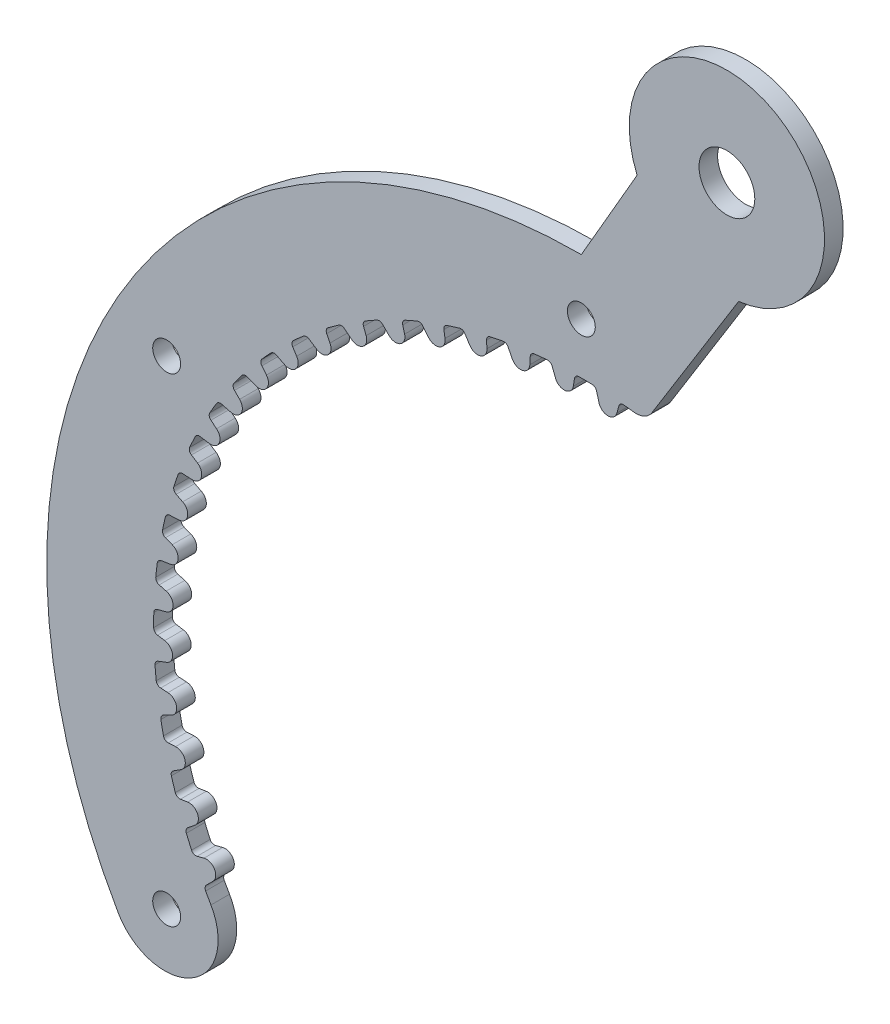
SolidWorks part; units mm, degrees
ref_plane "前视基准面" through (0, 0, 0) normal (0, 0, 1) x (1, 0, 0)
ref_plane "上视基准面" through (0, 0, 0) normal (0, 1, 0) x (1, 0, 0)
ref_plane "右视基准面" through (0, 0, 0) normal (1, 0, 0) x (0, 0, -1)
sketch "草图1" plane through (0, 0, 0) normal (0, 0, 1) x (1, 0, 0)
  line L6 (6.1601, 44.3885) -> (6.4016, 45.1318) [skipped]
  line L7 (0, 57.5) -> (6, 67.8923)
  line L10 (16.9119, 61.5923) -> (6.9151, 45.4773)
  line L11 (4.2309, 44.4896) -> (4.0233, 45.4665) [skipped]
  line L12 (3.8285, 44.65) -> (4.0308, 45.405)
  line L13 (1.8967, 44.65) -> (1.6382, 45.6147)
  line L14 (8.4748, 44.0052) -> (8.7549, 44.7349) [skipped]
  line L15 (6.5535, 44.2072) -> (6.3973, 45.1936) [skipped]
  line L16 (10.7662, 43.5014) -> (11.0841, 44.2154) [skipped]
  line L17 (8.8582, 43.8036) -> (8.7538, 44.7969) [skipped]
  line L164 (-37.109, -25.1238) -> (-37.823, -25.4417) [skipped]
  line L165 (-35.8932, -26.6252) -> (-36.4803, -27.4332) [skipped]
  line L166 (-38.373, -23.1473) -> (-39.1026, -23.4274) [skipped]
  line L167 (-37.2375, -24.7102) -> (-37.866, -25.4863) [skipped]
  line L168 (-39.5318, -21.1073) -> (-40.2752, -21.3488) [skipped]
  line L169 (-38.4797, -22.7274) -> (-39.148, -23.4697) [skipped]
  line L170 (-40.5823, -19.0094) -> (-41.3373, -19.2117)
  line L171 (-39.6164, -20.6824) -> (-40.3226, -21.3886)
  line L172 (-41.5216, -16.8594) -> (-42.2861, -17.0219) [skipped]
  line L173 (-40.6446, -18.5807) -> (-41.3868, -19.249) [skipped]
  line L174 (-42.347, -14.6633) -> (-43.119, -14.7855)
  line L175 (-41.5613, -16.4281) -> (-42.3375, -17.0566)
  line L176 (-43.0564, -12.4269) -> (-43.8337, -12.5086) [skipped]
  line L177 (-42.3641, -14.2304) -> (-43.1721, -14.8175) [skipped]
  line L178 (-43.6478, -10.1565) -> (-44.4283, -10.1974)
  line L179 (-43.0508, -11.9938) -> (-43.8884, -12.5377)
  line L180 (-44.1195, -7.8582) -> (-44.9011, -7.8582) [skipped]
  line L181 (-43.6195, -9.7242) -> (-44.4845, -10.2236) [skipped]
  line L182 (-44.4703, -5.5384) -> (-45.2508, -5.4975)
  line L183 (-44.0687, -7.428) -> (-44.9586, -7.8814)
  line L184 (-44.6992, -3.2034) -> (-45.4765, -3.1217) [skipped]
  line L185 (-44.397, -5.1115) -> (-45.3094, -5.5177) [skipped]
  line L186 (-44.8056, -0.8596) -> (-45.5776, -0.7374)
  line L187 (-44.6037, -2.7809) -> (-45.5361, -3.1388)
  line L188 (-44.7892, 1.4865) -> (-45.5537, 1.649) [skipped]
  line L189 (-44.6881, -0.4427) -> (-45.638, -0.7513) [skipped]
  line L190 (-44.65, 3.8285) -> (-45.405, 4.0308)
  line L191 (-44.65, 1.8967) -> (-45.6147, 1.6382)
  line L192 (-44.3885, 6.1601) -> (-45.1318, 6.4016) [skipped]
  line L193 (-44.4896, 4.2309) -> (-45.4665, 4.0233) [skipped]
  line L194 (-44.0052, 8.4748) -> (-44.7349, 8.7549)
  line L195 (-44.2072, 6.5535) -> (-45.1936, 6.3973)
  line L196 (-43.5014, 10.7662) -> (-44.2154, 11.0841) [skipped]
  line L197 (-43.8036, 8.8582) -> (-44.7969, 8.7538) [skipped]
  line L198 (-42.8783, 13.0282) -> (-43.5747, 13.383)
  line L199 (-43.28, 11.1385) -> (-44.2773, 11.0862)
  line L200 (-42.1377, 15.2544) -> (-42.8146, 15.6452) [skipped]
  line L201 (-42.6377, 13.3883) -> (-43.6365, 13.3883) [skipped]
  line L202 (-41.2816, 17.4388) -> (-41.9371, 17.8645)
  line L203 (-41.8786, 15.6015) -> (-42.876, 15.6538)
  line L204 (-40.3124, 19.5754) -> (-40.9447, 20.0348) [skipped]
  line L205 (-41.0047, 17.7719) -> (-41.9979, 17.8763) [skipped]
  line L206 (-39.2326, 21.6584) -> (-39.84, 22.1502)
  line L207 (-40.0184, 19.8935) -> (-41.0048, 20.0498)
  line L208 (-38.0454, 23.682) -> (-38.6262, 24.2049) [skipped]
  line L209 (-38.9224, 21.9607) -> (-39.8993, 22.1683) [skipped]
  line L210 (-36.7538, 25.6406) -> (-37.3064, 26.1933)
  line L211 (-37.7197, 23.9676) -> (-38.6844, 24.2261)
  line L212 (-35.3615, 27.529) -> (-35.8845, 28.1099) [skipped]
  line L213 (-36.4137, 25.9089) -> (-37.3635, 26.2175) [skipped]
  line L214 (-33.8723, 29.342) -> (-34.3641, 29.9494)
  line L215 (-35.0078, 27.7791) -> (-35.9402, 28.137)
  line L216 (-32.2902, 31.0745) -> (-32.7496, 31.7068) [skipped]
  line L217 (-33.506, 29.5732) -> (-34.4184, 29.9794) [skipped]
  line L218 (-30.6196, 32.7219) -> (-31.0453, 33.3773)
  line L219 (-31.9123, 31.2862) -> (-32.8022, 31.7396)
  line L220 (-28.8652, 34.2795) -> (-29.2559, 34.9564) [skipped]
  line L221 (-30.2312, 32.9135) -> (-31.0961, 33.4129) [skipped]
  line L222 (-27.0315, 35.7432) -> (-27.3864, 36.4396)
  line L223 (-28.4672, 34.4506) -> (-29.3048, 34.9945)
  line L224 (-25.1238, 37.109) -> (-25.4417, 37.823) [skipped]
  line L225 (-26.6252, 35.8932) -> (-27.4332, 36.4803) [skipped]
  line L226 (-23.1473, 38.373) -> (-23.4274, 39.1026)
  line L227 (-24.7102, 37.2375) -> (-25.4863, 37.866)
  line L228 (-21.1073, 39.5318) -> (-21.3488, 40.2752) [skipped]
  line L229 (-22.7274, 38.4797) -> (-23.4697, 39.148) [skipped]
  line L230 (-19.0094, 40.5823) -> (-19.2117, 41.3373)
  line L231 (-20.6824, 39.6164) -> (-21.3886, 40.3226)
  line L232 (-16.8594, 41.5216) -> (-17.0219, 42.2861) [skipped]
  line L233 (-18.5807, 40.6446) -> (-19.249, 41.3868) [skipped]
  line L234 (-14.6633, 42.347) -> (-14.7855, 43.119)
  line L235 (-16.4281, 41.5613) -> (-17.0566, 42.3375)
  line L236 (-12.4269, 43.0564) -> (-12.5086, 43.8337) [skipped]
  line L237 (-14.2304, 42.3641) -> (-14.8175, 43.1721) [skipped]
  line L238 (-10.1565, 43.6478) -> (-10.1974, 44.4283)
  line L239 (-11.9938, 43.0508) -> (-12.5377, 43.8884)
  line L240 (-7.8582, 44.1195) -> (-7.8582, 44.9011) [skipped]
  line L241 (-9.7242, 43.6195) -> (-10.2236, 44.4845) [skipped]
  line L242 (-5.5384, 44.4703) -> (-5.4975, 45.2508)
  line L243 (-7.428, 44.0687) -> (-7.8814, 44.9586)
  line L244 (-3.2034, 44.6992) -> (-3.1217, 45.4765) [skipped]
  line L245 (-5.1115, 44.397) -> (-5.5177, 45.3094) [skipped]
  line L246 (-0.8596, 44.8056) -> (-0.7374, 45.5776)
  line L247 (-2.7809, 44.6037) -> (-3.1388, 45.5361)
  line L248 (1.4865, 44.7892) -> (1.649, 45.5537) [skipped]
  line L249 (-0.4427, 44.6881) -> (-0.7513, 45.638) [skipped]
  line L250 (21.6584, 39.2326) -> (22.1502, 39.84) [skipped]
  line L251 (23.682, 38.0454) -> (24.2049, 38.6262) [skipped]
  line L252 (21.9607, 38.9224) -> (22.1683, 39.8993) [skipped]
  line L253 (25.6406, 36.7538) -> (26.1933, 37.3064) [skipped]
  line L254 (23.9676, 37.7197) -> (24.2261, 38.6844) [skipped]
  line L255 (27.529, 35.3615) -> (28.1099, 35.8845) [skipped]
  line L256 (25.9089, 36.4137) -> (26.2175, 37.3635) [skipped]
  line L257 (29.342, 33.8723) -> (29.9494, 34.3641) [skipped]
  line L258 (27.7791, 35.0078) -> (28.137, 35.9402) [skipped]
  line L259 (31.0745, 32.2902) -> (31.7068, 32.7496) [skipped]
  line L260 (29.5732, 33.506) -> (29.9794, 34.4184) [skipped]
  line L261 (32.7219, 30.6196) -> (33.3773, 31.0453) [skipped]
  line L262 (31.2862, 31.9123) -> (31.7396, 32.8022) [skipped]
  line L263 (34.2795, 28.8652) -> (34.9564, 29.2559) [skipped]
  line L264 (32.9135, 30.2312) -> (33.4129, 31.0961) [skipped]
  line L265 (35.7432, 27.0315) -> (36.4396, 27.3864) [skipped]
  line L266 (34.4506, 28.4672) -> (34.9945, 29.3048) [skipped]
  line L267 (37.109, 25.1238) -> (37.823, 25.4417) [skipped]
  line L268 (35.8932, 26.6252) -> (36.4803, 27.4332) [skipped]
  line L269 (38.373, 23.1473) -> (39.1026, 23.4274) [skipped]
  line L270 (37.2375, 24.7102) -> (37.866, 25.4863) [skipped]
  line L271 (39.5318, 21.1073) -> (40.2752, 21.3488) [skipped]
  line L272 (38.4797, 22.7274) -> (39.148, 23.4697) [skipped]
  line L273 (40.5823, 19.0094) -> (41.3373, 19.2117) [skipped]
  line L274 (39.6164, 20.6824) -> (40.3226, 21.3886) [skipped]
  line L275 (41.5216, 16.8594) -> (42.2861, 17.0219) [skipped]
  line L276 (40.6446, 18.5807) -> (41.3868, 19.249) [skipped]
  line L277 (42.347, 14.6633) -> (43.119, 14.7855) [skipped]
  line L278 (41.5613, 16.4281) -> (42.3375, 17.0566) [skipped]
  line L279 (43.0564, 12.4269) -> (43.8337, 12.5086) [skipped]
  line L280 (42.3641, 14.2304) -> (43.1721, 14.8175) [skipped]
  line L281 (43.6478, 10.1565) -> (44.4283, 10.1974) [skipped]
  line L282 (43.0508, 11.9938) -> (43.8884, 12.5377) [skipped]
  line L283 (44.1195, 7.8582) -> (44.9011, 7.8582) [skipped]
  line L284 (43.6195, 9.7242) -> (44.4845, 10.2236) [skipped]
  line L285 (44.4703, 5.5384) -> (45.2508, 5.4975) [skipped]
  line L286 (44.0687, 7.428) -> (44.9586, 7.8814) [skipped]
  line L287 (44.6992, 3.2034) -> (45.4765, 3.1217) [skipped]
  line L288 (44.397, 5.1115) -> (45.3094, 5.5177) [skipped]
  line L289 (44.8056, 0.8596) -> (45.5776, 0.7374) [skipped]
  line L290 (44.6037, 2.7809) -> (45.5361, 3.1388) [skipped]
  line L291 (44.7892, -1.4865) -> (45.5537, -1.649) [skipped]
  line L292 (44.6881, 0.4427) -> (45.638, 0.7513) [skipped]
  line L293 (44.65, -3.8285) -> (45.405, -4.0308) [skipped]
  line L294 (44.65, -1.8967) -> (45.6147, -1.6382) [skipped]
  line L295 (44.3885, -6.1601) -> (45.1318, -6.4016) [skipped]
  line L296 (44.4896, -4.2309) -> (45.4665, -4.0233) [skipped]
  line L297 (44.0052, -8.4748) -> (44.7349, -8.7549) [skipped]
  line L298 (44.2072, -6.5535) -> (45.1936, -6.3973) [skipped]
  line L299 (43.5014, -10.7662) -> (44.2154, -11.0841) [skipped]
  line L300 (43.8036, -8.8582) -> (44.7969, -8.7538) [skipped]
  line L301 (42.8783, -13.0282) -> (43.5747, -13.383) [skipped]
  line L302 (43.28, -11.1385) -> (44.2773, -11.0862) [skipped]
  line L303 (42.1377, -15.2544) -> (42.8146, -15.6452) [skipped]
  line L304 (42.6377, -13.3883) -> (43.6365, -13.3883) [skipped]
  line L305 (41.2816, -17.4388) -> (41.9371, -17.8645) [skipped]
  line L306 (41.8786, -15.6015) -> (42.876, -15.6538) [skipped]
  line L307 (40.3124, -19.5754) -> (40.9447, -20.0348) [skipped]
  line L308 (41.0047, -17.7719) -> (41.9979, -17.8763) [skipped]
  line L309 (39.2326, -21.6584) -> (39.84, -22.1502) [skipped]
  line L310 (40.0184, -19.8935) -> (41.0048, -20.0498) [skipped]
  line L311 (38.0454, -23.682) -> (38.6262, -24.2049) [skipped]
  line L312 (38.9224, -21.9607) -> (39.8993, -22.1683) [skipped]
  line L313 (36.7538, -25.6406) -> (37.3064, -26.1933) [skipped]
  line L314 (37.7197, -23.9676) -> (38.6844, -24.2261) [skipped]
  line L315 (35.3615, -27.529) -> (35.8845, -28.1099) [skipped]
  line L316 (36.4137, -25.9089) -> (37.3635, -26.2175) [skipped]
  line L317 (33.8723, -29.342) -> (34.3641, -29.9494) [skipped]
  line L318 (35.0078, -27.7791) -> (35.9402, -28.137) [skipped]
  line L319 (32.2902, -31.0745) -> (32.7496, -31.7068) [skipped]
  line L320 (33.506, -29.5732) -> (34.4184, -29.9794) [skipped]
  line L321 (30.6196, -32.7219) -> (31.0453, -33.3773) [skipped]
  line L322 (31.9123, -31.2862) -> (32.8022, -31.7396) [skipped]
  line L323 (28.8652, -34.2795) -> (29.2559, -34.9564) [skipped]
  line L324 (30.2312, -32.9135) -> (31.0961, -33.4129) [skipped]
  line L325 (27.0315, -35.7432) -> (27.3864, -36.4396) [skipped]
  line L326 (28.4672, -34.4506) -> (29.3048, -34.9945) [skipped]
  line L327 (25.1238, -37.109) -> (25.4417, -37.823) [skipped]
  line L328 (26.6252, -35.8932) -> (27.4332, -36.4803) [skipped]
  line L329 (23.1473, -38.373) -> (23.4274, -39.1026) [skipped]
  line L330 (24.7102, -37.2375) -> (25.4863, -37.866) [skipped]
  line L331 (21.1073, -39.5318) -> (21.3488, -40.2752) [skipped]
  line L332 (22.7274, -38.4797) -> (23.4697, -39.148) [skipped]
  line L333 (19.0094, -40.5823) -> (19.2117, -41.3373) [skipped]
  line L334 (20.6824, -39.6164) -> (21.3886, -40.3226) [skipped]
  line L335 (16.8594, -41.5216) -> (17.0219, -42.2861) [skipped]
  line L336 (18.5807, -40.6446) -> (19.249, -41.3868) [skipped]
  line L337 (14.6633, -42.347) -> (14.7855, -43.119) [skipped]
  line L338 (16.4281, -41.5613) -> (17.0566, -42.3375) [skipped]
  line L339 (12.4269, -43.0564) -> (12.5086, -43.8337) [skipped]
  line L340 (14.2304, -42.3641) -> (14.8175, -43.1721) [skipped]
  line L341 (10.1565, -43.6478) -> (10.1974, -44.4283) [skipped]
  line L342 (11.9938, -43.0508) -> (12.5377, -43.8884) [skipped]
  line L343 (7.8582, -44.1195) -> (7.8582, -44.9011) [skipped]
  line L344 (9.7242, -43.6195) -> (10.2236, -44.4845) [skipped]
  line L345 (5.5384, -44.4703) -> (5.4975, -45.2508) [skipped]
  line L346 (7.428, -44.0687) -> (7.8814, -44.9586) [skipped]
  line L347 (3.2034, -44.6992) -> (3.1217, -45.4765) [skipped]
  line L348 (5.1115, -44.397) -> (5.5177, -45.3094) [skipped]
  line L349 (0.8596, -44.8056) -> (0.7374, -45.5776) [skipped]
  line L350 (2.7809, -44.6037) -> (3.1388, -45.5361) [skipped]
  line L351 (-1.4865, -44.7892) -> (-1.649, -45.5537) [skipped]
  line L352 (0.4427, -44.6881) -> (0.7513, -45.638) [skipped]
  line L353 (-3.8285, -44.65) -> (-4.0308, -45.405) [skipped]
  line L354 (-1.8967, -44.65) -> (-1.6382, -45.6147) [skipped]
  line L355 (-6.1601, -44.3885) -> (-6.4016, -45.1318) [skipped]
  line L356 (-4.2309, -44.4896) -> (-4.0233, -45.4665) [skipped]
  line L357 (-8.4748, -44.0052) -> (-8.7549, -44.7349) [skipped]
  line L358 (-6.5535, -44.2072) -> (-6.3973, -45.1936) [skipped]
  line L359 (-10.7662, -43.5014) -> (-11.0841, -44.2154) [skipped]
  line L360 (-8.8582, -43.8036) -> (-8.7538, -44.7969) [skipped]
  line L361 (-13.0282, -42.8783) -> (-13.383, -43.5747) [skipped]
  line L362 (-11.1385, -43.28) -> (-11.0862, -44.2773) [skipped]
  line L363 (-15.2544, -42.1377) -> (-15.6452, -42.8146) [skipped]
  line L364 (-13.3883, -42.6377) -> (-13.3883, -43.6365) [skipped]
  line L365 (-17.4388, -41.2816) -> (-17.8645, -41.9371) [skipped]
  line L366 (-15.6015, -41.8786) -> (-15.6538, -42.876) [skipped]
  line L367 (-19.5754, -40.3124) -> (-20.0348, -40.9447) [skipped]
  line L368 (-17.7719, -41.0047) -> (-17.8763, -41.9979) [skipped]
  line L369 (-21.6584, -39.2326) -> (-22.1502, -39.84) [skipped]
  line L370 (-19.8935, -40.0184) -> (-20.0498, -41.0048) [skipped]
  line L371 (-23.682, -38.0454) -> (-24.2049, -38.6262) [skipped]
  line L372 (-21.9607, -38.9224) -> (-22.1683, -39.8993) [skipped]
  line L373 (-25.6406, -36.7538) -> (-26.1933, -37.3064) [skipped]
  line L374 (-23.9676, -37.7197) -> (-24.2261, -38.6844) [skipped]
  line L375 (-27.529, -35.3615) -> (-28.1099, -35.8845) [skipped]
  line L376 (-25.9089, -36.4137) -> (-26.2175, -37.3635) [skipped]
  line L377 (-29.342, -33.8723) -> (-29.9494, -34.3641) [skipped]
  line L378 (-27.7791, -35.0078) -> (-28.137, -35.9402) [skipped]
  line L379 (-31.0745, -32.2902) -> (-31.7068, -32.7496) [skipped]
  line L380 (-29.5732, -33.506) -> (-29.9794, -34.4184) [skipped]
  line L381 (-32.7219, -30.6196) -> (-33.3773, -31.0453) [skipped]
  line L382 (-31.2862, -31.9123) -> (-31.7396, -32.8022) [skipped]
  line L383 (-34.2795, -28.8652) -> (-34.9564, -29.2559) [skipped]
  line L384 (-32.9135, -30.2312) -> (-33.4129, -31.0961) [skipped]
  line L385 (-35.7432, -27.0315) -> (-36.4396, -27.3864) [skipped]
  line L386 (-34.4506, -28.4672) -> (-34.9945, -29.3048) [skipped]
  line L387 (13.0282, 42.8783) -> (13.383, 43.5747) [skipped]
  line L388 (11.1385, 43.28) -> (11.0862, 44.2773) [skipped]
  line L389 (15.2544, 42.1377) -> (15.6452, 42.8146) [skipped]
  line L390 (13.3883, 42.6377) -> (13.3883, 43.6365) [skipped]
  line L391 (17.4388, 41.2816) -> (17.8645, 41.9371) [skipped]
  line L392 (15.6015, 41.8786) -> (15.6538, 42.876) [skipped]
  line L393 (19.5754, 40.3124) -> (20.0348, 40.9447) [skipped]
  line L394 (17.7719, 41.0047) -> (17.8763, 41.9979) [skipped]
  line L395 (19.8935, 40.0184) -> (20.0498, 41.0048) [skipped]
  arc A0 (0, 57.5) -> (-49.7965, -28.75) centre (0, 0) ccw
  arc A2 (6.9151, 45.4773) -> (4.5634, 45.7731) centre (0, 0) ccw
  arc A3 (-49.7965, -28.75) -> (-39.8372, -23) centre (-44.8168, -25.875) ccw
  circle A4 centre (15.656, 72.0169) radius 3
  arc A5 (16.9119, 61.5923) -> (6, 67.8923) centre (15.656, 72.0169) ccw
  arc A12 (4.5634, 45.7731) -> (4.0308, 45.405) centre (4.5138, 45.2756) ccw
  arc A90 (1.8967, 44.65) -> (3.8285, 44.65) centre (2.8626, 44.9089) ccw
  arc A140 (1.6382, 45.6147) -> (1.1679, 45.9852) centre (1.1552, 45.4853) ccw
  arc A141 (4.2309, 44.4896) -> (6.1601, 44.3885) centre (5.209, 44.6975) ccw [skipped]
  arc A142 (6.9527, 45.4715) -> (6.4016, 45.1318) centre (6.8771, 44.9773) ccw [skipped]
  arc A143 (4.0233, 45.4665) -> (3.573, 45.861) centre (3.5342, 45.3625) ccw [skipped]
  arc A144 (6.5535, 44.2072) -> (8.4748, 44.0052) centre (7.5412, 44.3636) ccw [skipped]
  arc A145 (9.323, 45.0453) -> (8.7549, 44.7349) centre (9.2216, 44.5557) ccw [skipped]
  arc A146 (6.3973, 45.1936) -> (5.9683, 45.6112) centre (5.9034, 45.1154) ccw [skipped]
  arc A147 (8.8582, 43.8036) -> (10.7662, 43.5014) centre (9.8527, 43.9081) ccw [skipped]
  arc A148 (11.6677, 44.4957) -> (11.0841, 44.2154) centre (11.5409, 44.012) ccw [skipped]
  arc A149 (8.7538, 44.7969) -> (8.3472, 45.2363) centre (8.2565, 44.7446) ccw [skipped]
  arc A150 (-3.6452, 45.8553) -> (-5.0531, 45.7216) centre (0, 0) ccw
  arc A151 (1.1679, 45.9852) -> (-0.2462, 45.9993) centre (0, 0) ccw
  arc A152 (-8.4184, 45.2231) -> (-9.8046, 44.943) centre (0, 0) ccw
  arc A153 (-13.0994, 44.0954) -> (-14.4487, 43.6719) centre (0, 0) ccw
  arc A154 (-17.6369, 42.4846) -> (-18.9345, 41.9224) centre (0, 0) ccw
  arc A155 (-21.9811, 40.4083) -> (-23.2129, 39.7135) centre (0, 0) ccw
  arc A156 (-26.0845, 37.8893) -> (-27.2369, 37.0695) centre (0, 0) ccw
  arc A157 (-29.9021, 34.9551) -> (-30.9625, 34.0194) centre (0, 0) ccw
  arc A158 (-33.3921, 31.638) -> (-34.3489, 30.5966) centre (0, 0) ccw
  arc A159 (-36.5163, 27.9743) -> (-37.359, 26.8386) centre (0, 0) ccw
  arc A160 (-39.2404, 24.004) -> (-39.9597, 22.7865) centre (0, 0) ccw
  arc A161 (-41.5345, 19.7708) -> (-42.1226, 18.4847) centre (0, 0) ccw
  arc A162 (-43.3736, 15.321) -> (-43.8241, 13.9804) centre (0, 0) ccw
  arc A163 (-44.7375, 10.7033) -> (-45.0453, 9.323) centre (0, 0) ccw
  arc A164 (-45.6112, 5.9683) -> (-45.7731, 4.5634) centre (0, 0) ccw
  arc A165 (-45.9852, 1.1679) -> (-45.9993, -0.2462) centre (0, 0) ccw
  arc A166 (-45.8553, -3.6452) -> (-45.7216, -5.0531) centre (0, 0) ccw
  arc A167 (-45.2231, -8.4184) -> (-44.943, -9.8046) centre (0, 0) ccw
  arc A168 (-44.0954, -13.0994) -> (-43.6719, -14.4487) centre (0, 0) ccw
  arc A169 (-42.4846, -17.6369) -> (-41.9224, -18.9345) centre (0, 0) ccw
  arc A170 (-40.4083, -21.9811) -> (-39.8372, -23) centre (0, 0) ccw
  arc A369 (-35.8932, -26.6252) -> (-37.109, -25.1238) centre (-36.7022, -26.0374) ccw [skipped]
  arc A370 (-38.4442, -25.2595) -> (-37.823, -25.4417) centre (-38.0263, -24.985) ccw [skipped]
  arc A371 (-36.4803, -27.4332) -> (-36.4722, -28.0317) centre (-36.0758, -27.7271) ccw [skipped]
  arc A372 (-37.2375, -24.7102) -> (-38.373, -23.1473) centre (-38.0146, -24.0809) ccw [skipped]
  arc A373 (-39.7135, -23.2129) -> (-39.1026, -23.4274) centre (-39.2818, -22.9606) ccw [skipped]
  arc A374 (-37.866, -25.4863) -> (-37.8893, -26.0845) centre (-37.4774, -25.801) ccw [skipped]
  arc A375 (-38.4797, -22.7274) -> (-39.5318, -21.1073) centre (-39.2228, -22.0583) ccw [skipped]
  arc A376 (-40.8739, -21.1026) -> (-40.2752, -21.3488) centre (-40.4297, -20.8732) ccw [skipped]
  arc A377 (-39.148, -23.4697) -> (-39.2025, -24.0658) centre (-38.7764, -23.8042) ccw [skipped]
  arc A378 (-39.6164, -20.6824) -> (-40.5823, -19.0094) centre (-40.3235, -19.9753) ccw
  arc A379 (-41.9224, -18.9345) -> (-41.3373, -19.2117) centre (-41.4667, -18.7287) ccw
  arc A380 (-40.3226, -21.3886) -> (-40.4083, -21.9811) centre (-39.9691, -21.7422) ccw
  arc A381 (-40.6446, -18.5807) -> (-41.5216, -16.8594) centre (-41.3137, -17.8376) ccw [skipped]
  arc A382 (-42.8559, -16.7145) -> (-42.2861, -17.0219) centre (-42.39, -16.5329) ccw [skipped]
  arc A383 (-41.3868, -19.249) -> (-41.5033, -19.8362) centre (-41.0522, -19.6206) ccw [skipped]
  arc A384 (-41.5613, -16.4281) -> (-42.347, -14.6633) centre (-42.1906, -15.6509) ccw
  arc A385 (-43.6719, -14.4487) -> (-43.119, -14.7855) centre (-43.1972, -14.2917) ccw
  arc A386 (-42.3375, -17.0566) -> (-42.4846, -17.6369) centre (-42.0228, -17.4452) ccw
  arc A387 (-42.3641, -14.2304) -> (-43.0564, -12.4269) centre (-42.9519, -13.4214) ccw [skipped]
  arc A388 (-44.3682, -12.1433) -> (-43.8337, -12.5086) centre (-43.886, -12.0113) ccw [skipped]
  arc A389 (-43.1721, -14.8175) -> (-43.3494, -15.3892) centre (-42.8782, -15.222) ccw [skipped]
  arc A390 (-43.0508, -11.9938) -> (-43.6478, -10.1565) centre (-43.5955, -11.1551) ccw
  arc A391 (-44.943, -9.8046) -> (-44.4283, -10.1974) centre (-44.4544, -9.698) ccw
  arc A392 (-43.8884, -12.5377) -> (-44.0954, -13.0994) centre (-43.6161, -12.957) ccw
  arc A393 (-43.6195, -9.7242) -> (-44.1195, -7.8582) centre (-44.1195, -8.8582) ccw [skipped]
  arc A394 (-45.3945, -7.439) -> (-44.9011, -7.8582) centre (-44.9011, -7.3582) ccw [skipped]
  arc A395 (-44.4845, -10.2236) -> (-44.7205, -10.7737) centre (-44.2345, -10.6566) ccw [skipped]
  arc A396 (-44.0687, -7.428) -> (-44.4703, -5.5384) centre (-44.5227, -6.537) ccw
  arc A397 (-45.7216, -5.0531) -> (-45.2508, -5.4975) centre (-45.2246, -4.9982) ccw
  arc A398 (-44.9586, -7.8814) -> (-45.2231, -8.4184) centre (-44.7316, -8.3269) ccw
  arc A399 (-44.397, -5.1115) -> (-44.6992, -3.2034) centre (-44.8038, -4.1979) ccw [skipped]
  arc A400 (-45.9234, -2.6533) -> (-45.4765, -3.1217) centre (-45.4242, -2.6244) ccw [skipped]
  arc A401 (-45.3094, -5.5177) -> (-45.6017, -6.0401) centre (-45.1061, -5.9745) ccw [skipped]
  arc A402 (-44.6037, -2.7809) -> (-44.8056, -0.8596) centre (-44.9621, -1.8473) ccw
  arc A403 (-45.9993, -0.2462) -> (-45.5776, -0.7374) centre (-45.4993, -0.2435) ccw
  arc A404 (-45.5361, -3.1388) -> (-45.8553, -3.6452) centre (-45.3569, -3.6056) ccw
  arc A405 (-44.6881, -0.4427) -> (-44.7892, 1.4865) centre (-44.9971, 0.5084) ccw [skipped]
  arc A406 (-45.9492, 2.1616) -> (-45.5537, 1.649) centre (-45.4497, 2.1381) ccw [skipped]
  arc A407 (-45.638, -0.7513) -> (-45.9833, -1.2403) centre (-45.4835, -1.2269) ccw [skipped]
  arc A408 (-44.65, 1.8967) -> (-44.65, 3.8285) centre (-44.9089, 2.8626) ccw
  arc A409 (-45.7731, 4.5634) -> (-45.405, 4.0308) centre (-45.2756, 4.5138) ccw
  arc A410 (-45.6147, 1.6382) -> (-45.9852, 1.1679) centre (-45.4853, 1.1552) ccw
  arc A411 (-44.4896, 4.2309) -> (-44.3885, 6.1601) centre (-44.6975, 5.209) ccw [skipped]
  arc A412 (-45.4715, 6.9527) -> (-45.1318, 6.4016) centre (-44.9773, 6.8771) ccw [skipped]
  arc A413 (-45.4665, 4.0233) -> (-45.861, 3.573) centre (-45.3625, 3.5342) ccw [skipped]
  arc A414 (-44.2072, 6.5535) -> (-44.0052, 8.4748) centre (-44.3636, 7.5412) ccw
  arc A415 (-45.0453, 9.323) -> (-44.7349, 8.7549) centre (-44.5557, 9.2216) ccw
  arc A416 (-45.1936, 6.3973) -> (-45.6112, 5.9683) centre (-45.1154, 5.9034) ccw
  arc A417 (-43.8036, 8.8582) -> (-43.5014, 10.7662) centre (-43.9081, 9.8527) ccw [skipped]
  arc A418 (-44.4957, 11.6677) -> (-44.2154, 11.0841) centre (-44.012, 11.5409) ccw [skipped]
  arc A419 (-44.7969, 8.7538) -> (-45.2363, 8.3472) centre (-44.7446, 8.2565) ccw [skipped]
  arc A420 (-43.28, 11.1385) -> (-42.8783, 13.0282) centre (-43.3323, 12.1371) ccw
  arc A421 (-43.8241, 13.9804) -> (-43.5747, 13.383) centre (-43.3477, 13.8285) ccw
  arc A422 (-44.2773, 11.0862) -> (-44.7375, 10.7033) centre (-44.2512, 10.5869) ccw
  arc A423 (-42.6377, 13.3883) -> (-42.1377, 15.2544) centre (-42.6377, 14.3883) ccw [skipped]
  arc A424 (-43.0323, 16.2548) -> (-42.8146, 15.6452) centre (-42.5646, 16.0782) ccw [skipped]
  arc A425 (-43.6365, 13.3883) -> (-44.116, 13.03) centre (-43.6365, 12.8883) ccw [skipped]
  arc A426 (-41.8786, 15.6015) -> (-41.2816, 17.4388) centre (-41.8263, 16.6001) ccw
  arc A427 (-42.1226, 18.4847) -> (-41.9371, 17.8645) centre (-41.6648, 18.2838) ccw
  arc A428 (-42.876, 15.6538) -> (-43.3736, 15.321) centre (-42.9021, 15.1544) ccw
  arc A429 (-41.0047, 17.7719) -> (-40.3124, 19.5754) centre (-40.9002, 18.7664) ccw [skipped]
  arc A430 (-41.0975, 20.6639) -> (-40.9447, 20.0348) centre (-40.6508, 20.4393) ccw [skipped]
  arc A431 (-41.9979, 17.8763) -> (-42.5123, 17.57) centre (-42.0502, 17.379) ccw [skipped]
  arc A432 (-40.0184, 19.8935) -> (-39.2326, 21.6584) centre (-39.8619, 20.8812) ccw
  arc A433 (-39.9597, 22.7865) -> (-39.84, 22.1502) centre (-39.5254, 22.5388) ccw
  arc A434 (-41.0048, 20.0498) -> (-41.5345, 19.7708) centre (-41.083, 19.5559) ccw
  arc A435 (-38.9224, 21.9607) -> (-38.0454, 23.682) centre (-38.7145, 22.9388) ccw [skipped]
  arc A436 (-38.7124, 24.8466) -> (-38.6262, 24.2049) centre (-38.2916, 24.5765) ccw [skipped]
  arc A437 (-39.8993, 22.1683) -> (-40.4429, 21.9175) centre (-40.0033, 21.6792) ccw [skipped]
  arc A438 (-37.7197, 23.9676) -> (-36.7538, 25.6406) centre (-37.4609, 24.9335) ccw
  arc A439 (-37.359, 26.8386) -> (-37.3064, 26.1933) centre (-36.9529, 26.5468) ccw
  arc A440 (-38.6844, 24.2261) -> (-39.2404, 24.004) centre (-38.8138, 23.7431) ccw
  arc A441 (-36.4137, 25.9089) -> (-35.3615, 27.529) centre (-36.1046, 26.8599) ccw [skipped]
  arc A442 (-35.9031, 28.757) -> (-35.8845, 28.1099) centre (-35.5129, 28.4444) ccw [skipped]
  arc A443 (-37.3635, 26.2175) -> (-37.9303, 26.0248) centre (-37.518, 25.742) ccw [skipped]
  arc A444 (-35.0078, 27.7791) -> (-33.8723, 29.342) centre (-34.6494, 28.7127) ccw
  arc A445 (-34.3489, 30.5966) -> (-34.3641, 29.9494) centre (-33.9756, 30.264) ccw
  arc A446 (-35.9402, 28.137) -> (-36.5163, 27.9743) centre (-36.1194, 27.6702) ccw
  arc A447 (-33.506, 29.5732) -> (-32.2902, 31.0745) centre (-33.0992, 30.4867) ccw [skipped]
  arc A448 (-32.7005, 32.3524) -> (-32.7496, 31.7068) centre (-32.3451, 32.0007) ccw [skipped]
  arc A449 (-34.4184, 29.9794) -> (-35.0022, 29.8471) centre (-34.6217, 29.5226) ccw [skipped]
  arc A450 (-31.9123, 31.2862) -> (-30.6196, 32.7219) centre (-31.4583, 32.1772) ccw
  arc A451 (-30.9625, 34.0194) -> (-31.0453, 33.3773) centre (-30.626, 33.6497) ccw
  arc A452 (-32.8022, 31.7396) -> (-33.3921, 31.638) centre (-33.0292, 31.2941) ccw
  arc A453 (-30.2312, 32.9135) -> (-28.8652, 34.2795) centre (-29.7312, 33.7795) ccw [skipped]
  arc A454 (-29.1397, 35.5933) -> (-29.2559, 34.9564) centre (-28.8229, 35.2064) ccw [skipped]
  arc A455 (-31.0961, 33.4129) -> (-31.6906, 33.3423) centre (-31.3461, 32.9799) ccw [skipped]
  arc A456 (-28.4672, 34.4506) -> (-27.0315, 35.7432) centre (-27.9225, 35.2893) ccw
  arc A457 (-27.2369, 37.0695) -> (-27.3864, 36.4396) centre (-26.9409, 36.6666) ccw
  arc A458 (-29.3048, 34.9945) -> (-29.9021, 34.9551) centre (-29.5771, 34.5752) ccw
  arc A459 (-26.6252, 35.8932) -> (-25.1238, 37.109) centre (-26.0374, 36.7022) ccw [skipped]
  arc A460 (-25.2595, 38.4442) -> (-25.4417, 37.823) centre (-24.985, 38.0263) ccw [skipped]
  arc A461 (-27.4332, 36.4803) -> (-28.0317, 36.4722) centre (-27.7271, 36.0758) ccw [skipped]
  arc A462 (-24.7102, 37.2375) -> (-23.1473, 38.373) centre (-24.0809, 38.0146) ccw
  arc A463 (-23.2129, 39.7135) -> (-23.4274, 39.1026) centre (-22.9606, 39.2818) ccw
  arc A464 (-25.4863, 37.866) -> (-26.0845, 37.8893) centre (-25.801, 37.4774) ccw
  arc A465 (-22.7274, 38.4797) -> (-21.1073, 39.5318) centre (-22.0583, 39.2228) ccw [skipped]
  arc A466 (-21.1026, 40.8739) -> (-21.3488, 40.2752) centre (-20.8732, 40.4297) ccw [skipped]
  arc A467 (-23.4697, 39.148) -> (-24.0658, 39.2025) centre (-23.8042, 38.7764) ccw [skipped]
  arc A468 (-20.6824, 39.6164) -> (-19.0094, 40.5823) centre (-19.9753, 40.3235) ccw
  arc A469 (-18.9345, 41.9224) -> (-19.2117, 41.3373) centre (-18.7287, 41.4667) ccw
  arc A470 (-21.3886, 40.3226) -> (-21.9811, 40.4083) centre (-21.7422, 39.9691) ccw
  arc A471 (-18.5807, 40.6446) -> (-16.8594, 41.5216) centre (-17.8376, 41.3137) ccw [skipped]
  arc A472 (-16.7145, 42.8559) -> (-17.0219, 42.2861) centre (-16.5329, 42.39) ccw [skipped]
  arc A473 (-19.249, 41.3868) -> (-19.8362, 41.5033) centre (-19.6206, 41.0522) ccw [skipped]
  arc A474 (-16.4281, 41.5613) -> (-14.6633, 42.347) centre (-15.6509, 42.1906) ccw
  arc A475 (-14.4487, 43.6719) -> (-14.7855, 43.119) centre (-14.2917, 43.1972) ccw
  arc A476 (-17.0566, 42.3375) -> (-17.6369, 42.4846) centre (-17.4452, 42.0228) ccw
  arc A477 (-14.2304, 42.3641) -> (-12.4269, 43.0564) centre (-13.4214, 42.9519) ccw [skipped]
  arc A478 (-12.1433, 44.3682) -> (-12.5086, 43.8337) centre (-12.0113, 43.886) ccw [skipped]
  arc A479 (-14.8175, 43.1721) -> (-15.3892, 43.3494) centre (-15.222, 42.8782) ccw [skipped]
  arc A480 (-11.9938, 43.0508) -> (-10.1565, 43.6478) centre (-11.1551, 43.5955) ccw
  arc A481 (-9.8046, 44.943) -> (-10.1974, 44.4283) centre (-9.698, 44.4544) ccw
  arc A482 (-12.5377, 43.8884) -> (-13.0994, 44.0954) centre (-12.957, 43.6161) ccw
  arc A483 (-9.7242, 43.6195) -> (-7.8582, 44.1195) centre (-8.8582, 44.1195) ccw [skipped]
  arc A484 (-7.439, 45.3945) -> (-7.8582, 44.9011) centre (-7.3582, 44.9011) ccw [skipped]
  arc A485 (-10.2236, 44.4845) -> (-10.7737, 44.7205) centre (-10.6566, 44.2345) ccw [skipped]
  arc A486 (-7.428, 44.0687) -> (-5.5384, 44.4703) centre (-6.537, 44.5227) ccw
  arc A487 (-5.0531, 45.7216) -> (-5.4975, 45.2508) centre (-4.9982, 45.2246) ccw
  arc A488 (-7.8814, 44.9586) -> (-8.4184, 45.2231) centre (-8.3269, 44.7316) ccw
  arc A489 (-5.1115, 44.397) -> (-3.2034, 44.6992) centre (-4.1979, 44.8038) ccw [skipped]
  arc A490 (-2.6533, 45.9234) -> (-3.1217, 45.4765) centre (-2.6244, 45.4242) ccw [skipped]
  arc A491 (-5.5177, 45.3094) -> (-6.0401, 45.6017) centre (-5.9745, 45.1061) ccw [skipped]
  arc A492 (-2.7809, 44.6037) -> (-0.8596, 44.8056) centre (-1.8473, 44.9621) ccw
  arc A493 (-0.2462, 45.9993) -> (-0.7374, 45.5776) centre (-0.2435, 45.4993) ccw
  arc A494 (-3.1388, 45.5361) -> (-3.6452, 45.8553) centre (-3.6056, 45.3569) ccw
  arc A495 (-0.4427, 44.6881) -> (1.4865, 44.7892) centre (0.5084, 44.9971) ccw [skipped]
  arc A496 (2.1616, 45.9492) -> (1.649, 45.5537) centre (2.1381, 45.4497) ccw [skipped]
  arc A497 (-0.7513, 45.638) -> (-1.2403, 45.9833) centre (-1.2269, 45.4835) ccw [skipped]
  arc A498 (19.8935, 40.0184) -> (21.6584, 39.2326) centre (20.8812, 39.8619) ccw [skipped]
  arc A499 (22.7865, 39.9597) -> (22.1502, 39.84) centre (22.5388, 39.5254) ccw [skipped]
  arc A500 (21.9607, 38.9224) -> (23.682, 38.0454) centre (22.9388, 38.7145) ccw [skipped]
  arc A501 (24.8466, 38.7124) -> (24.2049, 38.6262) centre (24.5765, 38.2916) ccw [skipped]
  arc A502 (22.1683, 39.8993) -> (21.9175, 40.4429) centre (21.6792, 40.0033) ccw [skipped]
  arc A503 (23.9676, 37.7197) -> (25.6406, 36.7538) centre (24.9335, 37.4609) ccw [skipped]
  arc A504 (26.8386, 37.359) -> (26.1933, 37.3064) centre (26.5468, 36.9529) ccw [skipped]
  arc A505 (24.2261, 38.6844) -> (24.004, 39.2404) centre (23.7431, 38.8138) ccw [skipped]
  arc A506 (25.9089, 36.4137) -> (27.529, 35.3615) centre (26.8599, 36.1046) ccw [skipped]
  arc A507 (28.757, 35.9031) -> (28.1099, 35.8845) centre (28.4444, 35.5129) ccw [skipped]
  arc A508 (26.2175, 37.3635) -> (26.0248, 37.9303) centre (25.742, 37.518) ccw [skipped]
  arc A509 (27.7791, 35.0078) -> (29.342, 33.8723) centre (28.7127, 34.6494) ccw [skipped]
  arc A510 (30.5966, 34.3489) -> (29.9494, 34.3641) centre (30.264, 33.9756) ccw [skipped]
  arc A511 (28.137, 35.9402) -> (27.9743, 36.5163) centre (27.6702, 36.1194) ccw [skipped]
  arc A512 (29.5732, 33.506) -> (31.0745, 32.2902) centre (30.4867, 33.0992) ccw [skipped]
  arc A513 (32.3524, 32.7005) -> (31.7068, 32.7496) centre (32.0007, 32.3451) ccw [skipped]
  arc A514 (29.9794, 34.4184) -> (29.8471, 35.0022) centre (29.5226, 34.6217) ccw [skipped]
  arc A515 (31.2862, 31.9123) -> (32.7219, 30.6196) centre (32.1772, 31.4583) ccw [skipped]
  arc A516 (34.0194, 30.9625) -> (33.3773, 31.0453) centre (33.6497, 30.626) ccw [skipped]
  arc A517 (31.7396, 32.8022) -> (31.638, 33.3921) centre (31.2941, 33.0292) ccw [skipped]
  arc A518 (32.9135, 30.2312) -> (34.2795, 28.8652) centre (33.7795, 29.7312) ccw [skipped]
  arc A519 (35.5933, 29.1397) -> (34.9564, 29.2559) centre (35.2064, 28.8229) ccw [skipped]
  arc A520 (33.4129, 31.0961) -> (33.3423, 31.6906) centre (32.9799, 31.3461) ccw [skipped]
  arc A521 (34.4506, 28.4672) -> (35.7432, 27.0315) centre (35.2893, 27.9225) ccw [skipped]
  arc A522 (37.0695, 27.2369) -> (36.4396, 27.3864) centre (36.6666, 26.9409) ccw [skipped]
  arc A523 (34.9945, 29.3048) -> (34.9551, 29.9021) centre (34.5752, 29.5771) ccw [skipped]
  arc A524 (35.8932, 26.6252) -> (37.109, 25.1238) centre (36.7022, 26.0374) ccw [skipped]
  arc A525 (38.4442, 25.2595) -> (37.823, 25.4417) centre (38.0263, 24.985) ccw [skipped]
  arc A526 (36.4803, 27.4332) -> (36.4722, 28.0317) centre (36.0758, 27.7271) ccw [skipped]
  arc A527 (37.2375, 24.7102) -> (38.373, 23.1473) centre (38.0146, 24.0809) ccw [skipped]
  arc A528 (39.7135, 23.2129) -> (39.1026, 23.4274) centre (39.2818, 22.9606) ccw [skipped]
  arc A529 (37.866, 25.4863) -> (37.8893, 26.0845) centre (37.4774, 25.801) ccw [skipped]
  arc A530 (38.4797, 22.7274) -> (39.5318, 21.1073) centre (39.2228, 22.0583) ccw [skipped]
  arc A531 (40.8739, 21.1026) -> (40.2752, 21.3488) centre (40.4297, 20.8732) ccw [skipped]
  arc A532 (39.148, 23.4697) -> (39.2025, 24.0658) centre (38.7764, 23.8042) ccw [skipped]
  arc A533 (39.6164, 20.6824) -> (40.5823, 19.0094) centre (40.3235, 19.9753) ccw [skipped]
  arc A534 (41.9224, 18.9345) -> (41.3373, 19.2117) centre (41.4667, 18.7287) ccw [skipped]
  arc A535 (40.3226, 21.3886) -> (40.4083, 21.9811) centre (39.9691, 21.7422) ccw [skipped]
  arc A536 (40.6446, 18.5807) -> (41.5216, 16.8594) centre (41.3137, 17.8376) ccw [skipped]
  arc A537 (42.8559, 16.7145) -> (42.2861, 17.0219) centre (42.39, 16.5329) ccw [skipped]
  arc A538 (41.3868, 19.249) -> (41.5033, 19.8362) centre (41.0522, 19.6206) ccw [skipped]
  arc A539 (41.5613, 16.4281) -> (42.347, 14.6633) centre (42.1906, 15.6509) ccw [skipped]
  arc A540 (43.6719, 14.4487) -> (43.119, 14.7855) centre (43.1972, 14.2917) ccw [skipped]
  arc A541 (42.3375, 17.0566) -> (42.4846, 17.6369) centre (42.0228, 17.4452) ccw [skipped]
  arc A542 (42.3641, 14.2304) -> (43.0564, 12.4269) centre (42.9519, 13.4214) ccw [skipped]
  arc A543 (44.3682, 12.1433) -> (43.8337, 12.5086) centre (43.886, 12.0113) ccw [skipped]
  arc A544 (43.1721, 14.8175) -> (43.3494, 15.3892) centre (42.8782, 15.222) ccw [skipped]
  arc A545 (43.0508, 11.9938) -> (43.6478, 10.1565) centre (43.5955, 11.1551) ccw [skipped]
  arc A546 (44.943, 9.8046) -> (44.4283, 10.1974) centre (44.4544, 9.698) ccw [skipped]
  arc A547 (43.8884, 12.5377) -> (44.0954, 13.0994) centre (43.6161, 12.957) ccw [skipped]
  arc A548 (43.6195, 9.7242) -> (44.1195, 7.8582) centre (44.1195, 8.8582) ccw [skipped]
  arc A549 (45.3945, 7.439) -> (44.9011, 7.8582) centre (44.9011, 7.3582) ccw [skipped]
  arc A550 (44.4845, 10.2236) -> (44.7205, 10.7737) centre (44.2345, 10.6566) ccw [skipped]
  arc A551 (44.0687, 7.428) -> (44.4703, 5.5384) centre (44.5227, 6.537) ccw [skipped]
  arc A552 (45.7216, 5.0531) -> (45.2508, 5.4975) centre (45.2246, 4.9982) ccw [skipped]
  arc A553 (44.9586, 7.8814) -> (45.2231, 8.4184) centre (44.7316, 8.3269) ccw [skipped]
  arc A554 (44.397, 5.1115) -> (44.6992, 3.2034) centre (44.8038, 4.1979) ccw [skipped]
  arc A555 (45.9234, 2.6533) -> (45.4765, 3.1217) centre (45.4242, 2.6244) ccw [skipped]
  arc A556 (45.3094, 5.5177) -> (45.6017, 6.0401) centre (45.1061, 5.9745) ccw [skipped]
  arc A557 (44.6037, 2.7809) -> (44.8056, 0.8596) centre (44.9621, 1.8473) ccw [skipped]
  arc A558 (45.9993, 0.2462) -> (45.5776, 0.7374) centre (45.4993, 0.2435) ccw [skipped]
  arc A559 (45.5361, 3.1388) -> (45.8553, 3.6452) centre (45.3569, 3.6056) ccw [skipped]
  arc A560 (44.6881, 0.4427) -> (44.7892, -1.4865) centre (44.9971, -0.5084) ccw [skipped]
  arc A561 (45.9492, -2.1616) -> (45.5537, -1.649) centre (45.4497, -2.1381) ccw [skipped]
  arc A562 (45.638, 0.7513) -> (45.9833, 1.2403) centre (45.4835, 1.2269) ccw [skipped]
  arc A563 (44.65, -1.8967) -> (44.65, -3.8285) centre (44.9089, -2.8626) ccw [skipped]
  arc A564 (45.7731, -4.5634) -> (45.405, -4.0308) centre (45.2756, -4.5138) ccw [skipped]
  arc A565 (45.6147, -1.6382) -> (45.9852, -1.1679) centre (45.4853, -1.1552) ccw [skipped]
  arc A566 (44.4896, -4.2309) -> (44.3885, -6.1601) centre (44.6975, -5.209) ccw [skipped]
  arc A567 (45.4715, -6.9527) -> (45.1318, -6.4016) centre (44.9773, -6.8771) ccw [skipped]
  arc A568 (45.4665, -4.0233) -> (45.861, -3.573) centre (45.3625, -3.5342) ccw [skipped]
  arc A569 (44.2072, -6.5535) -> (44.0052, -8.4748) centre (44.3636, -7.5412) ccw [skipped]
  arc A570 (45.0453, -9.323) -> (44.7349, -8.7549) centre (44.5557, -9.2216) ccw [skipped]
  arc A571 (45.1936, -6.3973) -> (45.6112, -5.9683) centre (45.1154, -5.9034) ccw [skipped]
  arc A572 (43.8036, -8.8582) -> (43.5014, -10.7662) centre (43.9081, -9.8527) ccw [skipped]
  arc A573 (44.4957, -11.6677) -> (44.2154, -11.0841) centre (44.012, -11.5409) ccw [skipped]
  arc A574 (44.7969, -8.7538) -> (45.2363, -8.3472) centre (44.7446, -8.2565) ccw [skipped]
  arc A575 (43.28, -11.1385) -> (42.8783, -13.0282) centre (43.3323, -12.1371) ccw [skipped]
  arc A576 (43.8241, -13.9804) -> (43.5747, -13.383) centre (43.3477, -13.8285) ccw [skipped]
  arc A577 (44.2773, -11.0862) -> (44.7375, -10.7033) centre (44.2512, -10.5869) ccw [skipped]
  arc A578 (42.6377, -13.3883) -> (42.1377, -15.2544) centre (42.6377, -14.3883) ccw [skipped]
  arc A579 (43.0323, -16.2548) -> (42.8146, -15.6452) centre (42.5646, -16.0782) ccw [skipped]
  arc A580 (43.6365, -13.3883) -> (44.116, -13.03) centre (43.6365, -12.8883) ccw [skipped]
  arc A581 (41.8786, -15.6015) -> (41.2816, -17.4388) centre (41.8263, -16.6001) ccw [skipped]
  arc A582 (42.1226, -18.4847) -> (41.9371, -17.8645) centre (41.6648, -18.2838) ccw [skipped]
  arc A583 (42.876, -15.6538) -> (43.3736, -15.321) centre (42.9021, -15.1544) ccw [skipped]
  arc A584 (41.0047, -17.7719) -> (40.3124, -19.5754) centre (40.9002, -18.7664) ccw [skipped]
  arc A585 (41.0975, -20.6639) -> (40.9447, -20.0348) centre (40.6508, -20.4393) ccw [skipped]
  arc A586 (41.9979, -17.8763) -> (42.5123, -17.57) centre (42.0502, -17.379) ccw [skipped]
  arc A587 (40.0184, -19.8935) -> (39.2326, -21.6584) centre (39.8619, -20.8812) ccw [skipped]
  arc A588 (39.9597, -22.7865) -> (39.84, -22.1502) centre (39.5254, -22.5388) ccw [skipped]
  arc A589 (41.0048, -20.0498) -> (41.5345, -19.7708) centre (41.083, -19.5559) ccw [skipped]
  arc A590 (38.9224, -21.9607) -> (38.0454, -23.682) centre (38.7145, -22.9388) ccw [skipped]
  arc A591 (38.7124, -24.8466) -> (38.6262, -24.2049) centre (38.2916, -24.5765) ccw [skipped]
  arc A592 (39.8993, -22.1683) -> (40.4429, -21.9175) centre (40.0033, -21.6792) ccw [skipped]
  arc A593 (37.7197, -23.9676) -> (36.7538, -25.6406) centre (37.4609, -24.9335) ccw [skipped]
  arc A594 (37.359, -26.8386) -> (37.3064, -26.1933) centre (36.9529, -26.5468) ccw [skipped]
  arc A595 (38.6844, -24.2261) -> (39.2404, -24.004) centre (38.8138, -23.7431) ccw [skipped]
  arc A596 (36.4137, -25.9089) -> (35.3615, -27.529) centre (36.1046, -26.8599) ccw [skipped]
  arc A597 (35.9031, -28.757) -> (35.8845, -28.1099) centre (35.5129, -28.4444) ccw [skipped]
  arc A598 (37.3635, -26.2175) -> (37.9303, -26.0248) centre (37.518, -25.742) ccw [skipped]
  arc A599 (35.0078, -27.7791) -> (33.8723, -29.342) centre (34.6494, -28.7127) ccw [skipped]
  arc A600 (34.3489, -30.5966) -> (34.3641, -29.9494) centre (33.9756, -30.264) ccw [skipped]
  arc A601 (35.9402, -28.137) -> (36.5163, -27.9743) centre (36.1194, -27.6702) ccw [skipped]
  arc A602 (33.506, -29.5732) -> (32.2902, -31.0745) centre (33.0992, -30.4867) ccw [skipped]
  arc A603 (32.7005, -32.3524) -> (32.7496, -31.7068) centre (32.3451, -32.0007) ccw [skipped]
  arc A604 (34.4184, -29.9794) -> (35.0022, -29.8471) centre (34.6217, -29.5226) ccw [skipped]
  arc A605 (31.9123, -31.2862) -> (30.6196, -32.7219) centre (31.4583, -32.1772) ccw [skipped]
  arc A606 (30.9625, -34.0194) -> (31.0453, -33.3773) centre (30.626, -33.6497) ccw [skipped]
  arc A607 (32.8022, -31.7396) -> (33.3921, -31.638) centre (33.0292, -31.2941) ccw [skipped]
  arc A608 (30.2312, -32.9135) -> (28.8652, -34.2795) centre (29.7312, -33.7795) ccw [skipped]
  arc A609 (29.1397, -35.5933) -> (29.2559, -34.9564) centre (28.8229, -35.2064) ccw [skipped]
  arc A610 (31.0961, -33.4129) -> (31.6906, -33.3423) centre (31.3461, -32.9799) ccw [skipped]
  arc A611 (28.4672, -34.4506) -> (27.0315, -35.7432) centre (27.9225, -35.2893) ccw [skipped]
  arc A612 (27.2369, -37.0695) -> (27.3864, -36.4396) centre (26.9409, -36.6666) ccw [skipped]
  arc A613 (29.3048, -34.9945) -> (29.9021, -34.9551) centre (29.5771, -34.5752) ccw [skipped]
  arc A614 (26.6252, -35.8932) -> (25.1238, -37.109) centre (26.0374, -36.7022) ccw [skipped]
  arc A615 (25.2595, -38.4442) -> (25.4417, -37.823) centre (24.985, -38.0263) ccw [skipped]
  arc A616 (27.4332, -36.4803) -> (28.0317, -36.4722) centre (27.7271, -36.0758) ccw [skipped]
  arc A617 (24.7102, -37.2375) -> (23.1473, -38.373) centre (24.0809, -38.0146) ccw [skipped]
  arc A618 (23.2129, -39.7135) -> (23.4274, -39.1026) centre (22.9606, -39.2818) ccw [skipped]
  arc A619 (25.4863, -37.866) -> (26.0845, -37.8893) centre (25.801, -37.4774) ccw [skipped]
  arc A620 (22.7274, -38.4797) -> (21.1073, -39.5318) centre (22.0583, -39.2228) ccw [skipped]
  arc A621 (21.1026, -40.8739) -> (21.3488, -40.2752) centre (20.8732, -40.4297) ccw [skipped]
  arc A622 (23.4697, -39.148) -> (24.0658, -39.2025) centre (23.8042, -38.7764) ccw [skipped]
  arc A623 (20.6824, -39.6164) -> (19.0094, -40.5823) centre (19.9753, -40.3235) ccw [skipped]
  arc A624 (18.9345, -41.9224) -> (19.2117, -41.3373) centre (18.7287, -41.4667) ccw [skipped]
  arc A625 (21.3886, -40.3226) -> (21.9811, -40.4083) centre (21.7422, -39.9691) ccw [skipped]
  arc A626 (18.5807, -40.6446) -> (16.8594, -41.5216) centre (17.8376, -41.3137) ccw [skipped]
  arc A627 (16.7145, -42.8559) -> (17.0219, -42.2861) centre (16.5329, -42.39) ccw [skipped]
  arc A628 (19.249, -41.3868) -> (19.8362, -41.5033) centre (19.6206, -41.0522) ccw [skipped]
  arc A629 (16.4281, -41.5613) -> (14.6633, -42.347) centre (15.6509, -42.1906) ccw [skipped]
  arc A630 (14.4487, -43.6719) -> (14.7855, -43.119) centre (14.2917, -43.1972) ccw [skipped]
  arc A631 (17.0566, -42.3375) -> (17.6369, -42.4846) centre (17.4452, -42.0228) ccw [skipped]
  arc A632 (14.2304, -42.3641) -> (12.4269, -43.0564) centre (13.4214, -42.9519) ccw [skipped]
  arc A633 (12.1433, -44.3682) -> (12.5086, -43.8337) centre (12.0113, -43.886) ccw [skipped]
  arc A634 (14.8175, -43.1721) -> (15.3892, -43.3494) centre (15.222, -42.8782) ccw [skipped]
  arc A635 (11.9938, -43.0508) -> (10.1565, -43.6478) centre (11.1551, -43.5955) ccw [skipped]
  arc A636 (9.8046, -44.943) -> (10.1974, -44.4283) centre (9.698, -44.4544) ccw [skipped]
  arc A637 (12.5377, -43.8884) -> (13.0994, -44.0954) centre (12.957, -43.6161) ccw [skipped]
  arc A638 (9.7242, -43.6195) -> (7.8582, -44.1195) centre (8.8582, -44.1195) ccw [skipped]
  arc A639 (7.439, -45.3945) -> (7.8582, -44.9011) centre (7.3582, -44.9011) ccw [skipped]
  arc A640 (10.2236, -44.4845) -> (10.7737, -44.7205) centre (10.6566, -44.2345) ccw [skipped]
  arc A641 (7.428, -44.0687) -> (5.5384, -44.4703) centre (6.537, -44.5227) ccw [skipped]
  arc A642 (5.0531, -45.7216) -> (5.4975, -45.2508) centre (4.9982, -45.2246) ccw [skipped]
  arc A643 (7.8814, -44.9586) -> (8.4184, -45.2231) centre (8.3269, -44.7316) ccw [skipped]
  arc A644 (5.1115, -44.397) -> (3.2034, -44.6992) centre (4.1979, -44.8038) ccw [skipped]
  arc A645 (2.6533, -45.9234) -> (3.1217, -45.4765) centre (2.6244, -45.4242) ccw [skipped]
  arc A646 (5.5177, -45.3094) -> (6.0401, -45.6017) centre (5.9745, -45.1061) ccw [skipped]
  arc A647 (2.7809, -44.6037) -> (0.8596, -44.8056) centre (1.8473, -44.9621) ccw [skipped]
  arc A648 (0.2462, -45.9993) -> (0.7374, -45.5776) centre (0.2435, -45.4993) ccw [skipped]
  arc A649 (3.1388, -45.5361) -> (3.6452, -45.8553) centre (3.6056, -45.3569) ccw [skipped]
  arc A650 (0.4427, -44.6881) -> (-1.4865, -44.7892) centre (-0.5084, -44.9971) ccw [skipped]
  arc A651 (-2.1616, -45.9492) -> (-1.649, -45.5537) centre (-2.1381, -45.4497) ccw [skipped]
  arc A652 (0.7513, -45.638) -> (1.2403, -45.9833) centre (1.2269, -45.4835) ccw [skipped]
  arc A653 (-1.8967, -44.65) -> (-3.8285, -44.65) centre (-2.8626, -44.9089) ccw [skipped]
  arc A654 (-4.5634, -45.7731) -> (-4.0308, -45.405) centre (-4.5138, -45.2756) ccw [skipped]
  arc A655 (-1.6382, -45.6147) -> (-1.1679, -45.9852) centre (-1.1552, -45.4853) ccw [skipped]
  arc A656 (-4.2309, -44.4896) -> (-6.1601, -44.3885) centre (-5.209, -44.6975) ccw [skipped]
  arc A657 (-6.9527, -45.4715) -> (-6.4016, -45.1318) centre (-6.8771, -44.9773) ccw [skipped]
  arc A658 (-4.0233, -45.4665) -> (-3.573, -45.861) centre (-3.5342, -45.3625) ccw [skipped]
  arc A659 (-6.5535, -44.2072) -> (-8.4748, -44.0052) centre (-7.5412, -44.3636) ccw [skipped]
  arc A660 (-9.323, -45.0453) -> (-8.7549, -44.7349) centre (-9.2216, -44.5557) ccw [skipped]
  arc A661 (-6.3973, -45.1936) -> (-5.9683, -45.6112) centre (-5.9034, -45.1154) ccw [skipped]
  arc A662 (-8.8582, -43.8036) -> (-10.7662, -43.5014) centre (-9.8527, -43.9081) ccw [skipped]
  arc A663 (-11.6677, -44.4957) -> (-11.0841, -44.2154) centre (-11.5409, -44.012) ccw [skipped]
  arc A664 (-8.7538, -44.7969) -> (-8.3472, -45.2363) centre (-8.2565, -44.7446) ccw [skipped]
  arc A665 (-11.1385, -43.28) -> (-13.0282, -42.8783) centre (-12.1371, -43.3323) ccw [skipped]
  arc A666 (-13.9804, -43.8241) -> (-13.383, -43.5747) centre (-13.8285, -43.3477) ccw [skipped]
  arc A667 (-11.0862, -44.2773) -> (-10.7033, -44.7375) centre (-10.5869, -44.2512) ccw [skipped]
  arc A668 (-13.3883, -42.6377) -> (-15.2544, -42.1377) centre (-14.3883, -42.6377) ccw [skipped]
  arc A669 (-16.2548, -43.0323) -> (-15.6452, -42.8146) centre (-16.0782, -42.5646) ccw [skipped]
  arc A670 (-13.3883, -43.6365) -> (-13.03, -44.116) centre (-12.8883, -43.6365) ccw [skipped]
  arc A671 (-15.6015, -41.8786) -> (-17.4388, -41.2816) centre (-16.6001, -41.8263) ccw [skipped]
  arc A672 (-18.4847, -42.1226) -> (-17.8645, -41.9371) centre (-18.2838, -41.6648) ccw [skipped]
  arc A673 (-15.6538, -42.876) -> (-15.321, -43.3736) centre (-15.1544, -42.9021) ccw [skipped]
  arc A674 (-17.7719, -41.0047) -> (-19.5754, -40.3124) centre (-18.7664, -40.9002) ccw [skipped]
  arc A675 (-20.6639, -41.0975) -> (-20.0348, -40.9447) centre (-20.4393, -40.6508) ccw [skipped]
  arc A676 (-17.8763, -41.9979) -> (-17.57, -42.5123) centre (-17.379, -42.0502) ccw [skipped]
  arc A677 (-19.8935, -40.0184) -> (-21.6584, -39.2326) centre (-20.8812, -39.8619) ccw [skipped]
  arc A678 (-22.7865, -39.9597) -> (-22.1502, -39.84) centre (-22.5388, -39.5254) ccw [skipped]
  arc A679 (-20.0498, -41.0048) -> (-19.7708, -41.5345) centre (-19.5559, -41.083) ccw [skipped]
  arc A680 (-21.9607, -38.9224) -> (-23.682, -38.0454) centre (-22.9388, -38.7145) ccw [skipped]
  arc A681 (-24.8466, -38.7124) -> (-24.2049, -38.6262) centre (-24.5765, -38.2916) ccw [skipped]
  arc A682 (-22.1683, -39.8993) -> (-21.9175, -40.4429) centre (-21.6792, -40.0033) ccw [skipped]
  arc A683 (-23.9676, -37.7197) -> (-25.6406, -36.7538) centre (-24.9335, -37.4609) ccw [skipped]
  arc A684 (-26.8386, -37.359) -> (-26.1933, -37.3064) centre (-26.5468, -36.9529) ccw [skipped]
  arc A685 (-24.2261, -38.6844) -> (-24.004, -39.2404) centre (-23.7431, -38.8138) ccw [skipped]
  arc A686 (-25.9089, -36.4137) -> (-27.529, -35.3615) centre (-26.8599, -36.1046) ccw [skipped]
  arc A687 (-28.757, -35.9031) -> (-28.1099, -35.8845) centre (-28.4444, -35.5129) ccw [skipped]
  arc A688 (-26.2175, -37.3635) -> (-26.0248, -37.9303) centre (-25.742, -37.518) ccw [skipped]
  arc A689 (-27.7791, -35.0078) -> (-29.342, -33.8723) centre (-28.7127, -34.6494) ccw [skipped]
  arc A690 (-30.5966, -34.3489) -> (-29.9494, -34.3641) centre (-30.264, -33.9756) ccw [skipped]
  arc A691 (-28.137, -35.9402) -> (-27.9743, -36.5163) centre (-27.6702, -36.1194) ccw [skipped]
  arc A692 (-29.5732, -33.506) -> (-31.0745, -32.2902) centre (-30.4867, -33.0992) ccw [skipped]
  arc A693 (-32.3524, -32.7005) -> (-31.7068, -32.7496) centre (-32.0007, -32.3451) ccw [skipped]
  arc A694 (-29.9794, -34.4184) -> (-29.8471, -35.0022) centre (-29.5226, -34.6217) ccw [skipped]
  arc A695 (-31.2862, -31.9123) -> (-32.7219, -30.6196) centre (-32.1772, -31.4583) ccw [skipped]
  arc A696 (-34.0194, -30.9625) -> (-33.3773, -31.0453) centre (-33.6497, -30.626) ccw [skipped]
  arc A697 (-31.7396, -32.8022) -> (-31.638, -33.3921) centre (-31.2941, -33.0292) ccw [skipped]
  arc A698 (-32.9135, -30.2312) -> (-34.2795, -28.8652) centre (-33.7795, -29.7312) ccw [skipped]
  arc A699 (-35.5933, -29.1397) -> (-34.9564, -29.2559) centre (-35.2064, -28.8229) ccw [skipped]
  arc A700 (-33.4129, -31.0961) -> (-33.3423, -31.6906) centre (-32.9799, -31.3461) ccw [skipped]
  arc A701 (-34.4506, -28.4672) -> (-35.7432, -27.0315) centre (-35.2893, -27.9225) ccw [skipped]
  arc A702 (-37.0695, -27.2369) -> (-36.4396, -27.3864) centre (-36.6666, -26.9409) ccw [skipped]
  arc A703 (-34.9945, -29.3048) -> (-34.9551, -29.9021) centre (-34.5752, -29.5771) ccw [skipped]
  arc A704 (11.1385, 43.28) -> (13.0282, 42.8783) centre (12.1371, 43.3323) ccw [skipped]
  arc A705 (13.9804, 43.8241) -> (13.383, 43.5747) centre (13.8285, 43.3477) ccw [skipped]
  arc A706 (11.0862, 44.2773) -> (10.7033, 44.7375) centre (10.5869, 44.2512) ccw [skipped]
  arc A707 (13.3883, 42.6377) -> (15.2544, 42.1377) centre (14.3883, 42.6377) ccw [skipped]
  arc A708 (16.2548, 43.0323) -> (15.6452, 42.8146) centre (16.0782, 42.5646) ccw [skipped]
  arc A709 (13.3883, 43.6365) -> (13.03, 44.116) centre (12.8883, 43.6365) ccw [skipped]
  arc A710 (15.6015, 41.8786) -> (17.4388, 41.2816) centre (16.6001, 41.8263) ccw [skipped]
  arc A711 (18.4847, 42.1226) -> (17.8645, 41.9371) centre (18.2838, 41.6648) ccw [skipped]
  arc A712 (15.6538, 42.876) -> (15.321, 43.3736) centre (15.1544, 42.9021) ccw [skipped]
  arc A713 (17.7719, 41.0047) -> (19.5754, 40.3124) centre (18.7664, 40.9002) ccw [skipped]
  arc A714 (20.6639, 41.0975) -> (20.0348, 40.9447) centre (20.4393, 40.6508) ccw [skipped]
  arc A715 (17.8763, 41.9979) -> (17.57, 42.5123) centre (17.379, 42.0502) ccw [skipped]
  arc A716 (20.0498, 41.0048) -> (19.7708, 41.5345) centre (19.5559, 41.083) ccw [skipped]
  point P21 (0, 0)
  point P22 (8.1339, 44.2588)
  point P23 (-38.9711, -22.5)
  dimension "D1" = 120
extrude "凸台-拉伸1" add sketch "草图1" along normal blind 2
fillet "圆角1" radius 2 1 edges at (6.9151, 45.4773, 1)
sketch "草图2" plane through (0, 0, 2) normal (0, 0, 1) x (1, 0, 0)
  arc A0 (0, 57.5) -> (-49.7965, -28.75) centre (0, 0) ccw construction
  arc A1 (0, 57.5) -> (-49.7965, -28.75) centre (0, 0) ccw
  circle A3 centre (0, 51.5) radius 1.5
  circle A4 centre (-44.6003, -25.75) radius 1.5
  circle A5 centre (-44.6003, 25.75) radius 1.5
extrude "切除-拉伸1" cut sketch "草图2" against normal blind 10 contours A5 | A4 | A3 region at (0, 51.5, 2) region at (-44.6003, -25.75, 2) region at (-44.6003, 25.75, 2)
